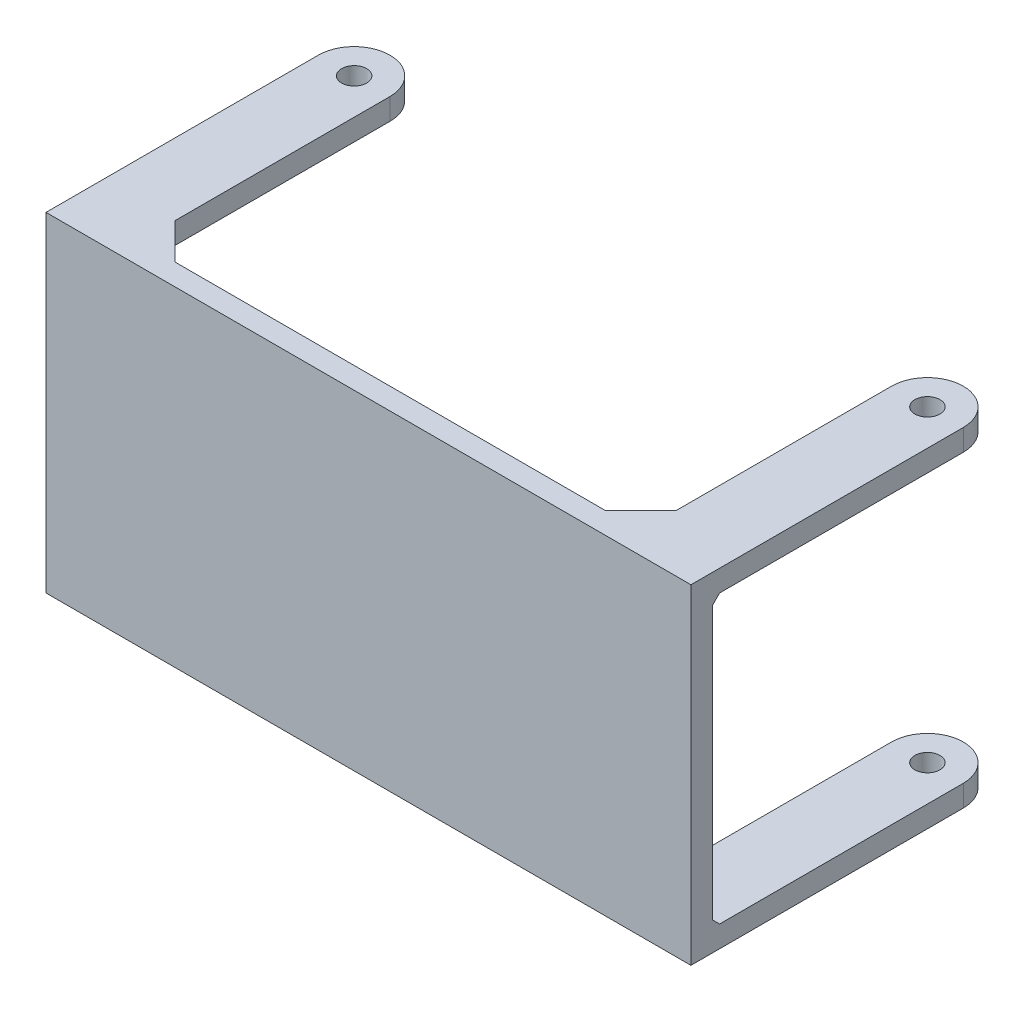
SolidWorks part; units mm, degrees
material "ABS"
ref_plane "Płaszczyzna przednia" through (0, 0, 0) normal (0, 0, 1) x (1, 0, 0)
ref_plane "Płaszczyzna górna" through (0, 0, 0) normal (0, 1, 0) x (1, 0, 0)
ref_plane "Płaszczyzna prawa" through (0, 0, 0) normal (1, 0, 0) x (0, 0, -1)
sketch "Szkic1" plane through (0, 0, 0) normal (0, 0, 1) x (1, 0, 0)
  line L1 (-45, -23) -> (45, -23)
  line L2 (-45, -23) -> (-45, 23)
  line L3 (-45, 23) -> (45, 23)
  line L4 (45, -23) -> (45, 23)
  line L5 (-45, -23) -> (45, 23) construction
  line L6 (-45, 23) -> (45, -23) construction
  point P0 (0, 0)
  dimension "D1" = 46
  dimension "D2" = 90
extrude "Dodanie-wyciągnięcie1" add sketch "Szkic1" along normal blind 3
sketch "Szkic2" plane through (0, 0, 0) normal (0, 0, -1) x (-1, 0, 0)
  line L1 (-45, 23) -> (-35, 23)
  line L2 (-45, 23) -> (-45, 20)
  line L3 (-45, 20) -> (-35, 20)
  line L4 (-35, 23) -> (-35, 20)
  line L5 (45, 23) -> (35, 23)
  line L6 (45, 23) -> (45, 20)
  line L7 (45, 20) -> (35, 20)
  line L8 (35, 23) -> (35, 20)
  dimension "D1" = 3
  dimension "D2" = 10
  dimension "D3" = 3
  dimension "D4" = 10
extrude "Dodanie-wyciągnięcie2" add sketch "Szkic2" along normal blind 40
chamfer "Sfazowanie1" distance 5 angle 45 2 edges at (-35, 21.5, 0) (35, 21.5, 0)
chamfer "Sfazowanie2" distance 1 angle 45 2 edges at (-37.5, 20, 0) (37.5, 20, 0)
fillet "Zaokrąglenie1" radius 5 4 edges at (35, 21.5, -40) (45, 21.5, -40) (-35, 21.5, -40) (-45, 21.5, -40)
mirror "Lustro1" about plane through (0, 0, 0) normal (0, 1, 0) of "Zaokrąglenie1", "Dodanie-wyciągnięcie2", "Sfazowanie1", "Sfazowanie2"
sketch "Szkic3" plane through (0, 23, 0) normal (0, 1, 0) x (1, 0, 0)
  circle A0 centre (-40, 35) radius 1.75
  circle A1 centre (40, 35) radius 1.75
  dimension "D1" = 3.5
extrude "Wytnij-wyciągnięcie1" cut sketch "Szkic3" against normal through all
